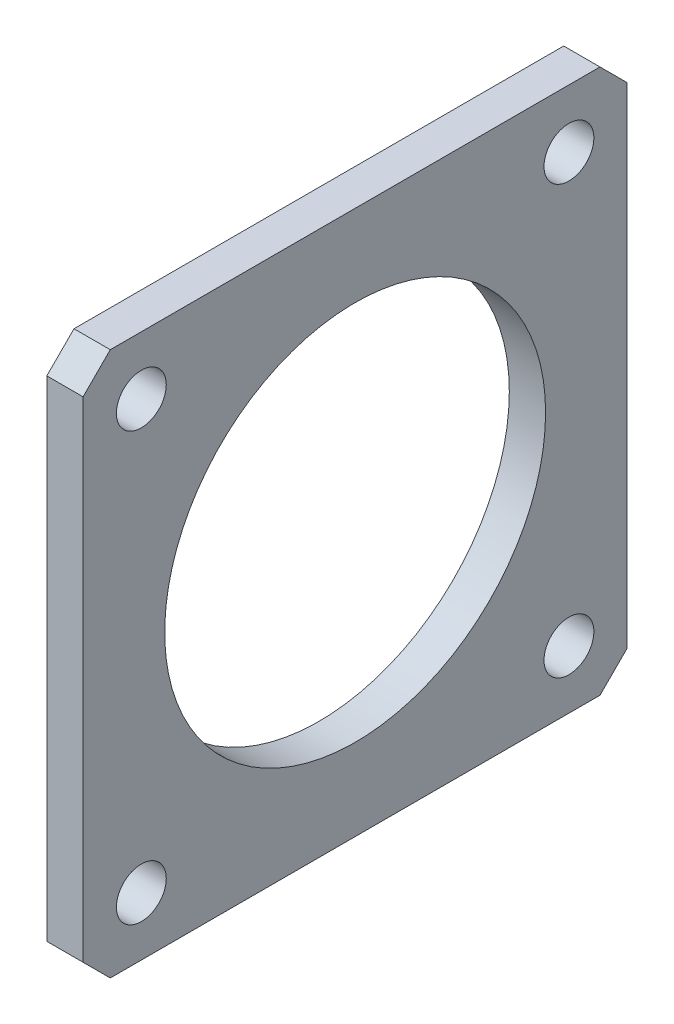
SolidWorks part; units mm, degrees
material "6063-T1"
ref_plane "Płaszczyzna przednia" through (0, 0, 0) normal (0, 0, 1) x (1, 0, 0)
ref_plane "Płaszczyzna górna" through (0, 0, 0) normal (0, 1, 0) x (1, 0, 0)
ref_plane "Płaszczyzna prawa" through (0, 0, 0) normal (1, 0, 0) x (0, 0, -1)
sketch "Szkic1" plane through (0, 0, 0) normal (1, 0, 0) x (0, 0, -1)
  line L1 (-30, 30) -> (30, 30)
  line L2 (-30, 30) -> (-30, -30)
  line L3 (-30, -30) -> (30, -30)
  line L4 (30, 30) -> (30, -30)
  line L5 (-30, 30) -> (30, -30) construction
  line L6 (-30, -30) -> (30, 30) construction
  circle A0 centre (0, 0) radius 21
  point P0 (0, 0)
  dimension "D2" = 42
  dimension "D1" = 60
base flange "Odgięcie bazowe1" sketch "Szkic1" thickness 4 reverse thickness direction no parameters "D1"=3
hole_wizard "Otwór pod śrubę M51" positions "Szkic6" profile "Szkic7" hole size "M5" standard "ISO"
sketch "Szkic6" plane through (0, 0, 0) normal (1, 0, 0) x (0, 0, -1)
  line L0 (0, 0) -> (0, 50000) construction
  line L1 (0, 0) -> (50000, 0) construction
  point P0 (-23.575, 23.575)
  point P9 (0, 0)
  point P10 (23.575, 23.575)
  point P11 (0, 0)
  point P12 (23.575, -23.575)
  point P13 (-23.575, -23.575)
  dimension "D1" = 47.15
  dimension "D2" = 47.15
sketch "Szkic7" plane through (0, 23.575, 23.575) normal (0, 1, 0) x (0, 0, -1)
  line L0 (0, 0) -> (0, 12.6524)
  line L1 (0, 12.6524) -> (2.75, 11)
  line L2 (2.75, 11) -> (2.75, 0)
  line L5 (2.75, 0) -> (0, 0)
  line L10 (0, 12.6524) -> (-2.75, 11) construction
  line L11 (0, -6.35) -> (0, 107.95) construction
  dimension "Średnica otworu" = 5.5
  dimension "Głębokość otworu" = 11
  dimension "Kąt wiertła" = 118
chamfer "Sfazowanie1" distance 3 angle 45 4 edges at (-2, -30, -30) (-2, 30, -30) (-2, -30, 30) (-2, 30, 30)
sketch "Linie zgięcia1" [suppressed] plane through (0, 0, 0) normal (0, 1, 0) x (1, 0, 0)
sketch "Ramka-graniczna1" [suppressed] plane through (0, 0, 0) normal (0, 1, 0) x (1, 0, 0)
sheet metal parameters "Arkusz blachy21" thickness 4 parameters "D1"=3
flat pattern "Rozłożony model21" [suppressed]
sketch "Linie zgięcia2" plane through (0, 0, 0) normal (0, 1, 0) x (1, 0, 0)
sketch "Ramka-graniczna2" [suppressed] plane through (0, 0, 0) normal (0, 1, 0) x (1, 0, 0)
sheet metal parameters "Arkusz blachy22" thickness 4 parameters "D1"=3
flat pattern "Rozłożony model21"
sketch "Linie zgięcia2" plane through (0, 0, 0) normal (0, 1, 0) x (1, 0, 0)
sketch3d "Ramka-graniczna2" [suppressed]
  line L0 (-30, -30, 0) -> (30, -30, 0) construction
  line L1 (-30, 30, 0) -> (30, 30, 0) construction
  line L2 (-30, -30, 0) -> (-30, 30, 0) construction
  line L3 (30, -30, 0) -> (30, 30, 0) construction
